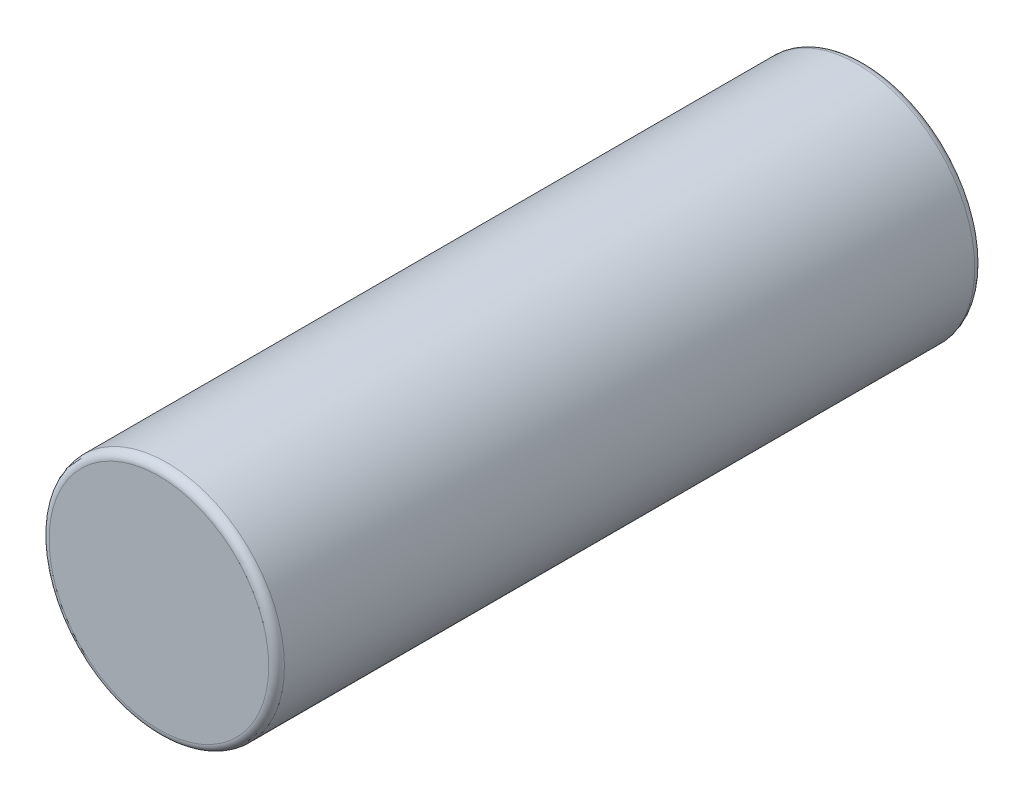
SolidWorks part; units mm, degrees
material "Aleación 1060"
ref_plane "Alzado" through (0, 0, 0) normal (0, 0, 1) x (1, 0, 0)
ref_plane "Planta" through (0, 0, 0) normal (0, 1, 0) x (1, 0, 0)
ref_plane "Vista lateral" through (0, 0, 0) normal (1, 0, 0) x (0, 0, -1)
sketch "Croquis1" plane through (0, 0, 0) normal (0, 0, 1) x (1, 0, 0)
  circle A0 centre (0, 0) radius 0.75
  dimension "D1" = 1.5
extrude "Saliente-Extruir1" add sketch "Croquis1" along normal blind 2.25 and the other way blind 2.25
fillet "Redondeo1" radius 0.05 2 edges at (0.75, 0, -2.25) (0.75, 0, 2.25)
